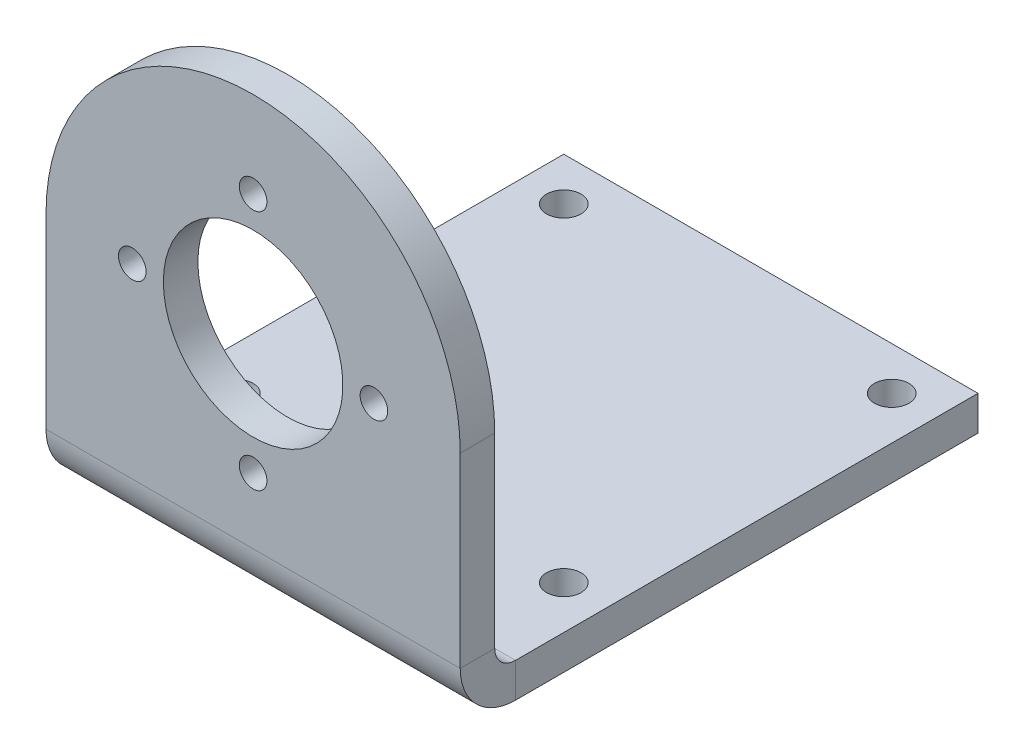
SolidWorks part; units mm, degrees
note: The reader was unsure of these and kept them because the rebuilt part matched: flange length of "边线-法兰2".
ref_plane "前视基准面" through (0, 0, 0) normal (0, 0, 1) x (1, 0, 0)
ref_plane "上视基准面" through (0, 0, 0) normal (0, 1, 0) x (1, 0, 0)
ref_plane "右视基准面" through (0, 0, 0) normal (1, 0, 0) x (0, 0, -1)
other "Configuration Table"
sketch "草图10" plane through (0, 0, 0) normal (0, 0, 1) x (1, 0, 0)
  line L1 (-30, -30) -> (30, -30)
  line L2 (-30, -30) -> (-30, 30)
  line L3 (-30, 30) -> (30, 30)
  line L4 (30, -30) -> (30, 30)
  line L5 (-30, -30) -> (30, 30) construction
  line L6 (-30, 30) -> (30, -30) construction
  point P0 (0, 0)
  dimension "D1" = 60
  dimension "D2" = 60
base flange "基体-法兰2" sketch "草图10" thickness 5 reverse thickness direction no parameters "D1"=0.7366
edge flange "边线-法兰2" sketch "草图17" flange angle 90 flange length 75 flange position material outside bend radius 3 thickness 5 relief rectangular parameters "D6"=10
sketch "草图17" plane through (0, -30, -5) normal (0, 1, 0) x (1, 0, 0)
  line L2 (-30, 0) -> (-30, 70)
  line L3 (-30, 70) -> (30, 70)
  line L4 (30, 70) -> (30, 0)
  line L5 (30, 0) -> (-30, 0) construction
  line L6 (30, 0) -> (-30, 0)
  dimension "D1" = 70
bend "边线折弯2" bend radius 3 bend angle 90 parameters "D5"=1
sketch "草图19" plane through (0, 0, 0) normal (0, 0, 1) x (1, 0, 0)
  line L0 (-1000, 0) -> (49000, 0) construction
  line L1 (0, -1000) -> (0, 49000) construction
  circle A0 centre (0, 0) radius 17.5 construction
  circle A1 centre (-17.5, 0) radius 2
  circle A2 centre (17.5, 0) radius 2
  circle A3 centre (0, 17.5) radius 2
  circle A4 centre (0, -17.5) radius 2
  circle A5 centre (0, 0) radius 13
  dimension "D1" = 35
  dimension "D2" = 4
  dimension "D3" = 4
  dimension "D4" = 4
  dimension "D5" = 4
  dimension "D6" = 26
extrude "切除-拉伸2" cut sketch "草图19" against normal up to surface (5 mm away) from surface at 0 up to face at (0, 1.5, -5) starting at face at (0, 1.5, 0)
sketch "草图28" plane through (0, 0, 0) normal (0, 1, 0) x (1, 0, 0)
  line L0 (30, 8) -> (30, 75) construction
  line L1 (-30, 75) -> (30, 75) construction
  line L2 (-30, 75) -> (-30, 15) construction
  line L3 (-30, 15) -> (30, 15) construction
  line L4 (30, 75) -> (30, 15) construction
  line L5 (-30, 75) -> (30, 15) construction
  line L6 (30, 75) -> (-30, 15) construction
  line L8 (-23.75, 21.25) -> (23.75, 21.25) construction
  line L9 (-23.75, 21.25) -> (-23.75, 68.75) construction
  line L10 (-23.75, 68.75) -> (23.75, 68.75) construction
  line L11 (23.75, 21.25) -> (23.75, 68.75) construction
  line L12 (-23.75, 21.25) -> (23.75, 68.75) construction
  line L13 (-23.75, 68.75) -> (23.75, 21.25) construction
  circle A0 centre (-23.75, 21.25) radius 2.5
  circle A1 centre (-23.75, 68.75) radius 2.5
  circle A2 centre (23.75, 68.75) radius 2.5
  circle A3 centre (23.75, 21.25) radius 2.5
  point P7 (0, 45)
  dimension "D4" = 5
  dimension "D5" = 5
  dimension "D6" = 5
  dimension "D7" = 5
  dimension "D1" = 60
  dimension "D2" = 47.5
  dimension "D3" = 47.5
extrude "切除-拉伸4" cut sketch "草图28" against normal up to surface (5 mm away) from surface at -30 up to face at (0, -35, -41.5) starting at face at (0, -30, -41.5)
sketch "草图29" plane through (0, 0, 0) normal (0, 0, 1) x (1, 0, 0)
  line L1 (0, 30) -> (-30, 30)
  line L4 (-30, 30) -> (-30, 0)
  line L6 (0, 30) -> (30, 30)
  line L9 (30, 30) -> (30, 0)
  arc A0 (30, 0) -> (-30, 0) centre (0, 0) ccw
  dimension "D1" = 60
extrude "切除-拉伸5" cut sketch "草图29" against normal up to surface (5 mm away) from surface at 0 contours A0 L1 L4 | A0 L9 L6 up to face at (-19.5, 0, -5) starting at face at (-19.5, 0, 0)
sketch "折弯-线3" plane through (0, 0, 0) normal (0, 1, 0) x (1, 0, 0)
sketch "边界框3" plane through (0, 0, 0) normal (0, 1, 0) x (1, 0, 0)
sheet metal parameters "钣金9" thickness 5 parameters "D1"=0.7366
flat pattern "平板型式9" [suppressed]
sketch "折弯-线4" plane through (0, 0, 0) normal (0, 1, 0) x (1, 0, 0)
sketch "边界框4" [suppressed] plane through (0, 0, 0) normal (0, 1, 0) x (1, 0, 0)
sheet metal parameters "钣金10" thickness 5 parameters "D1"=0.7366
flat pattern "平板型式9" [suppressed]
sketch "折弯-线4" plane through (0, 0, 0) normal (0, 1, 0) x (1, 0, 0)
sketch "边界框4" [suppressed] plane through (0, 0, 0) normal (0, 1, 0) x (1, 0, 0)
bend of the flat pattern "展平-<边线折弯2>1"
sheet metal parameters "钣金11" thickness 5 parameters "D1"=0.7366
flat pattern "平板型式9" [suppressed]
sketch "折弯-线4" plane through (0, 0, 0) normal (0, 1, 0) x (1, 0, 0)
sketch "边界框4" [suppressed] plane through (0, 0, 0) normal (0, 1, 0) x (1, 0, 0)
bend of the flat pattern "展平-<边线折弯2>1"
sheet metal parameters "钣金14" thickness 5 parameters "D1"=0.7366
flat pattern "平板型式9" [suppressed]
sketch "折弯-线4" plane through (0, 0, 0) normal (0, 1, 0) x (1, 0, 0)
sketch "边界框4" [suppressed] plane through (0, 0, 0) normal (0, 1, 0) x (1, 0, 0)
bend of the flat pattern "展平-<边线折弯2>1"
sheet metal parameters "钣金15" thickness 5 parameters "D1"=0.7366
flat pattern "平板型式9" [suppressed]
sketch "折弯-线4" plane through (0, 0, 0) normal (0, 1, 0) x (1, 0, 0)
sketch "边界框4" [suppressed] plane through (0, 0, 0) normal (0, 1, 0) x (1, 0, 0)
bend of the flat pattern "展平-<边线折弯2>1"
